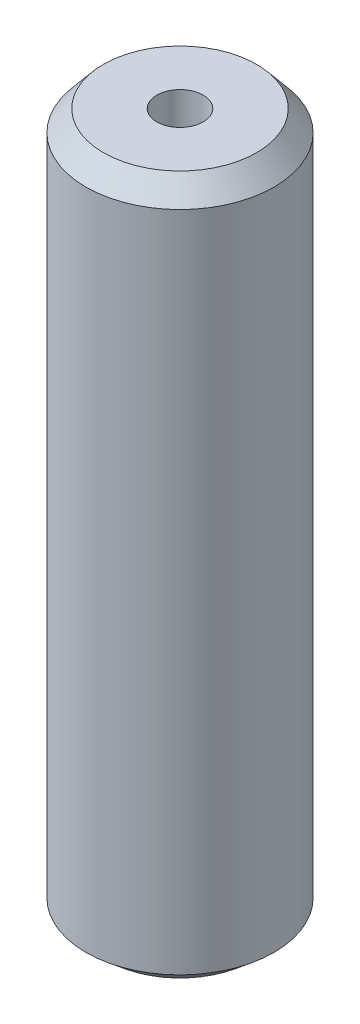
SolidWorks part; units mm, degrees
ref_plane "Front Plane" through (0, 0, 0) normal (0, 0, 1) x (1, 0, 0)
ref_plane "Top Plane" through (0, 0, 0) normal (0, 1, 0) x (1, 0, 0)
ref_plane "Right Plane" through (0, 0, 0) normal (1, 0, 0) x (0, 0, -1)
sketch "Sketch1" plane through (0, 0, 0) normal (0, 1, 0) x (1, 0, 0)
  circle A0 centre (0, 0) radius 10
  dimension "SHAFT_OD" = 20
extrude "Boss-Extrude1" add sketch "Sketch1" along normal blind 74.5189
sketch "Sketch2" plane through (0, 0, 0) normal (0, 1, 0) x (1, 0, 0)
  circle A0 centre (0, 0) radius 2.4662
  dimension "BORE_D" = 4.9324
extrude "Cut-Extrude1" cut sketch "Sketch2" along normal through all
chamfer "Chamfer1" distance 2.2297 angle 39.899 2 edges at (0, 74.5189, 10) (0, 0, 10) first distance on face at (0, 74.5189, 10) first distance on face at (0, 0, 2.4662)
